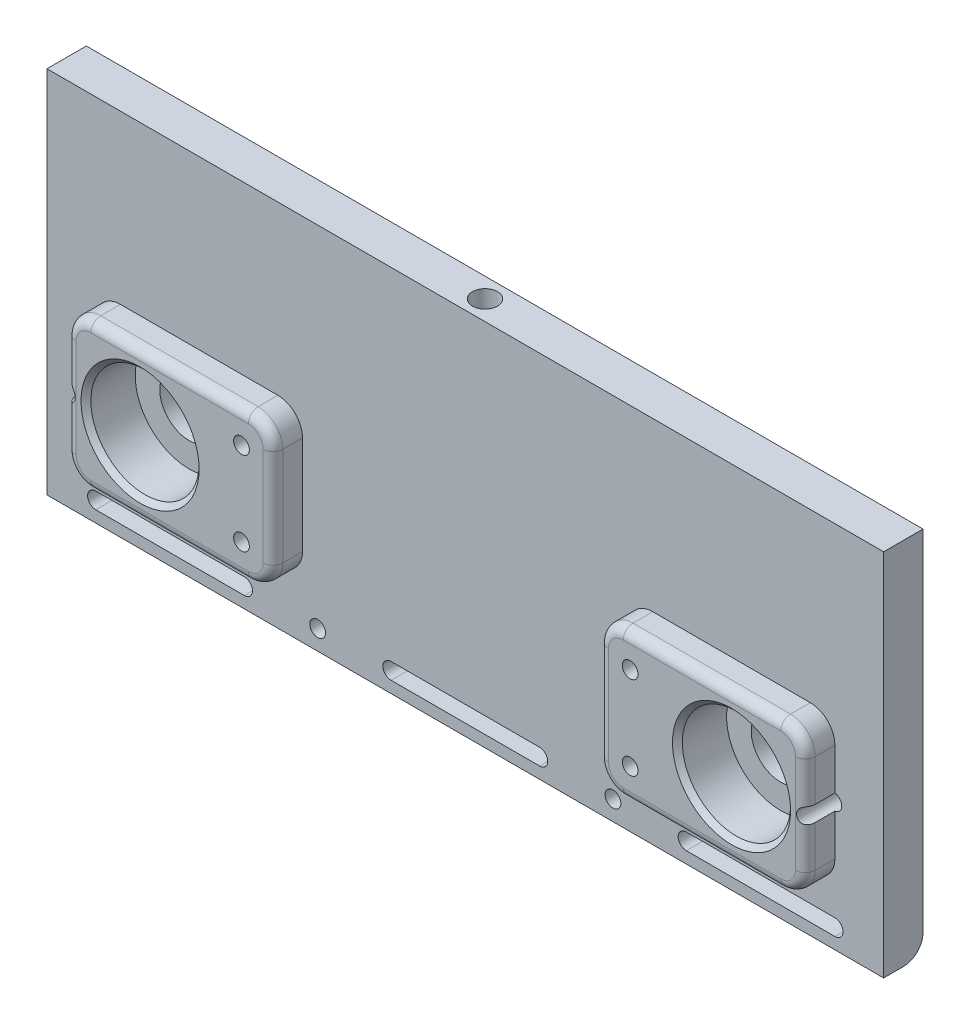
SolidWorks part; units mm, degrees
ref_plane "Ön Düzlem" through (0, 0, 0) normal (0, 0, 1) x (1, 0, 0)
ref_plane "Üst Düzlem" through (0, 0, 0) normal (0, 1, 0) x (1, 0, 0)
ref_plane "Sağ Düzlem" through (0, 0, 0) normal (1, 0, 0) x (0, 0, -1)
sketch "Çizim1" plane through (0, 0, 0) normal (0, 0, 1) x (1, 0, 0)
  line L0 (-153.241, -57.5) -> (171.9592, -57.5) construction
  line L1 (-85, 37.5) -> (85, 37.5)
  line L2 (-85, 37.5) -> (-85, -37.5)
  line L3 (-85, -37.5) -> (85, -37.5)
  line L4 (85, 37.5) -> (85, -37.5)
  line L5 (-85, 37.5) -> (85, -37.5) construction
  line L6 (-85, -37.5) -> (85, 37.5) construction
  circle A1 centre (39.97, -20.6736) radius 15 construction
  circle A2 centre (68.8351, -12.5) radius 15 construction
  circle A3 centre (-39.97, -20.6736) radius 15 construction
  circle A4 centre (-68.8351, -12.5) radius 15 construction
  circle A5 centre (-68.8351, -12.5) radius 45 construction
  circle A6 centre (68.8351, -12.5) radius 45 construction
  circle A7 centre (0, 0) radius 30 construction
  point P0 (0, 0)
  dimension "D2" = 170
  dimension "D3" = 30
  dimension "D5" = 90
  dimension "D7" = 60
  dimension "D1" = 75
  dimension "D6" = 20
extrude "Yükseklik-Ekstrüzyon1" add sketch "Çizim1" along normal mid plane 8 contours L1 L4 L3 L2
sketch "Çizim2" plane through (0, 0, 0) normal (0, 0, 1) x (1, 0, 0)
  line L0 (-15.1, -33.5) -> (15.1, -33.5) construction
  line L1 (-15.1, -31.85) -> (15.1, -31.85)
  line L2 (-15.1, -35.15) -> (15.1, -35.15)
  line L3 (-75.1, -33.5) -> (-44.9, -33.5) construction
  line L4 (-75.1, -31.85) -> (-44.9, -31.85)
  line L5 (-75.1, -35.15) -> (-44.9, -35.15)
  line L6 (44.9, -33.5) -> (75.1, -33.5) construction
  line L7 (44.9, -31.85) -> (75.1, -31.85)
  line L8 (44.9, -35.15) -> (75.1, -35.15)
  line L9 (-60, -33.5) -> (60, -33.5) construction
  line L10 (-85, -37.5) -> (85, -37.5) construction
  line L11 (-85, 37.5) -> (-85, -37.5) construction
  arc A0 (-15.1, -31.85) -> (-15.1, -35.15) centre (-15.1, -33.5) ccw
  arc A1 (15.1, -35.15) -> (15.1, -31.85) centre (15.1, -33.5) ccw
  arc A2 (-75.1, -31.85) -> (-75.1, -35.15) centre (-75.1, -33.5) ccw
  arc A3 (-44.9, -35.15) -> (-44.9, -31.85) centre (-44.9, -33.5) ccw
  arc A4 (44.9, -31.85) -> (44.9, -35.15) centre (44.9, -33.5) ccw
  arc A5 (75.1, -35.15) -> (75.1, -31.85) centre (75.1, -33.5) ccw
  point P2 (0, -33.5)
  point P8 (-60, -33.5)
  point P15 (60, -33.5)
  point P23 (0, -33.5)
  dimension "D1" = 1.65
  dimension "D2" = 30.2
  dimension "D3" = 4
  dimension "D4" = 25
extrude "Kes-Ekstrüzyon1" cut sketch "Çizim2" along normal through all
sketch "Çizim3" plane through (0, 0, 0) normal (0, 0, 1) x (1, 0, 0)
  line L0 (30, -33.5) -> (-30, -33.5) construction
  line L1 (-85, -37.5) -> (85, -37.5) construction
  circle A0 centre (30, -33.5) radius 1.6
  circle A1 centre (-30, -33.5) radius 1.6
  point P4 (0, -33.5)
  point P8 (0, -37.5)
  dimension "D1" = 3.2
  dimension "D2" = 55
  dimension "D3" = 4
extrude "Kes-Ekstrüzyon2" cut sketch "Çizim3" against normal mid plane 10
sketch "Çizim4" plane through (0, 0, -4) normal (0, 0, -1) x (-1, 0, 0)
  circle A0 centre (-30, -33.5) radius 3.4
  circle A1 centre (30, -33.5) radius 3.4
  circle A3 centre (-30, -33.5) radius 1.6 construction
  circle A4 centre (30, -33.5) radius 1.6 construction
  dimension "D1" = 6.8
extrude "Kes-Ekstrüzyon3" cut sketch "Çizim4" against normal blind 2.7
fillet "Radyus1" radius 4 1 edges at (0, -37.5, -4)
sketch "Çizim5" plane through (0, 37.5, 0) normal (0, 1, 0) x (1, 0, 0)
  circle A0 centre (0, 0) radius 2.55
  dimension "D1" = 5.1
extrude "Kes-Ekstrüzyon4" cut sketch "Çizim5" against normal blind 12
sketch "Çizim6" plane through (0, 0, 0) normal (0, 0, 1) x (1, 0, 0)
  line L0 (-85, -37.5) -> (85, -37.5) construction
  line L1 (-85, 37.5) -> (-85, -37.5) construction
  circle A0 centre (-60.08, -11.5) radius 6
  circle A1 centre (60.09, -11.5) radius 6
  dimension "D4" = 12
  dimension "D1" = 120.17
  dimension "D2" = 26
  dimension "D3" = 24.92
sketch "Çizim7" plane through (0, 0, 4) normal (0, 0, 1) x (1, 0, 0)
  circle A0 centre (-60.08, -11.5) radius 11
  circle A1 centre (60.09, -11.5) radius 11
  circle A2 centre (60.09, -11.5) radius 6 construction
  circle A3 centre (-60.08, -11.5) radius 6 construction
  dimension "D1" = 22
extrude "Kes-Ekstrüzyon5" cut sketch "Çizim7" against normal blind 4
extrude "Kes-Ekstrüzyon6" cut sketch "Çizim6" against normal mid plane 15 contours A1 | A0 region at (60.09, -11.5, 0)
sketch "Çizim8" plane through (0, 0, 4) normal (0, 0, 1) x (1, 0, 0)
  line L0 (-39.48, -3) -> (-39.48, -20) construction
  line L1 (-75.08, 3.5) -> (-33.08, 3.5)
  line L2 (-75.08, 3.5) -> (-75.08, -26.5)
  line L3 (-75.08, -26.5) -> (-33.08, -26.5)
  line L4 (-33.08, 3.5) -> (-33.08, -26.5)
  line L5 (33.09, 3.5) -> (75.09, 3.5)
  line L6 (33.09, 3.5) -> (33.09, -26.5)
  line L7 (33.09, -26.5) -> (75.09, -26.5)
  line L8 (75.09, 3.5) -> (75.09, -26.5)
  circle A0 centre (-60.08, -11.5) radius 11
  circle A1 centre (60.09, -11.5) radius 11
  circle A4 centre (-60.08, -11.5) radius 11 construction
  circle A5 centre (60.09, -11.5) radius 11 construction
  circle A6 centre (-39.48, -3) radius 1.6
  circle A7 centre (-39.48, -20) radius 1.6
  circle A8 centre (39.49, -3) radius 1.6
  circle A9 centre (39.49, -20) radius 1.6
  point P20 (-75.08, -11.5)
  point P27 (-39.48, -11.5)
  point P28 (-33.08, -11.5)
  dimension "D6" = 3.2
  dimension "D1" = 30
  dimension "D2" = 15
  dimension "D3" = 27
  dimension "D4" = 15
  dimension "D5" = 17
  dimension "D7" = 20.6
  dimension "D8" = 20.6
extrude "Yükseklik-Ekstrüzyon2" add sketch "Çizim8" along normal blind 6
sketch "Çizim9" plane through (0, 0, 4) normal (0, 0, 1) x (1, 0, 0)
  circle A0 centre (-39.48, -3) radius 1.6
  circle A1 centre (-39.48, -20) radius 1.6
  circle A2 centre (39.49, -3) radius 1.6
  circle A3 centre (39.49, -20) radius 1.6
  circle A4 centre (39.49, -20) radius 1.6 construction
  circle A5 centre (39.49, -3) radius 1.6 construction
  circle A6 centre (-39.48, -3) radius 1.6 construction
  circle A7 centre (-39.48, -20) radius 1.6 construction
extrude "Kes-Ekstrüzyon7" cut sketch "Çizim9" against normal through all
fillet "Radyus2" radius 5 8 edges at (75.09, 3.5, 7) (75.09, -26.5, 7) (33.09, -26.5, 7) (33.09, 3.5, 7) (-33.08, -26.5, 7) (-75.08, -26.5, 7) (-75.08, 3.5, 7) (-33.08, 3.5, 7)
sketch "Çizim10" plane through (0, 0, 4) normal (0, 0, 1) x (1, 0, 0)
  line L0 (-33.08, -21.5) -> (-33.08, -1.5) construction
  circle A0 centre (-74.88, -11.5) radius 1.6
  circle A1 centre (74.89, -11.5) radius 1.6
  circle A2 centre (-39.48, -3) radius 1.6 construction
  circle A3 centre (-60.08, -11.5) radius 6 construction
  circle A4 centre (60.09, -11.5) radius 6 construction
  point P12 (-33.08, -11.5)
  dimension "D1" = 14.8
  dimension "D2" = 14.8
extrude "Kes-Ekstrüzyon8" cut sketch "Çizim10" against normal mid plane 30
sketch "Çizim11" plane through (0, 0, -4) normal (0, 0, -1) x (-1, 0, 0)
  circle A0 centre (-74.89, -11.5) radius 3.4
  circle A1 centre (-39.49, -3) radius 3.4
  circle A2 centre (-39.49, -20) radius 3.4
  circle A3 centre (39.48, -3) radius 3.4
  circle A4 centre (39.48, -20) radius 3.4
  circle A5 centre (74.88, -11.5) radius 3.4
  circle A6 centre (-74.89, -11.5) radius 1.6 construction
  circle A7 centre (-39.49, -3) radius 1.6 construction
  circle A8 centre (-39.49, -20) radius 1.6 construction
  circle A9 centre (39.48, -3) radius 1.6 construction
  circle A10 centre (39.48, -20) radius 1.6 construction
  circle A11 centre (74.88, -11.5) radius 1.6 construction
  dimension "D1" = 6.8
extrude "Kes-Ekstrüzyon9" cut sketch "Çizim11" against normal blind 3
fillet "Radyus3" radius 2 16 edges at (73.6255, 2.0355, 10) (75.09, -17.2937, 10) (73.6255, -25.0355, 10) (54.09, -26.5, 10) (34.5545, -25.0355, 10) (33.09, -11.5, 10) (34.5545, 2.0355, 10) (-73.6155, -25.0355, 10) (-54.08, -26.5, 10) (-34.5445, -25.0355, 10) (-33.08, -11.5, 10) (-34.5445, 2.0355, 10) (-75.08, -5.7063, 10) (-73.6155, 2.0355, 10) (54.09, 3.5, 10) (-54.08, 3.5, 10)
chamfer "Pah1" distance 1 angle 45 2 edges at (71.09, -11.5, 10) (-49.08, -11.5, 10)
